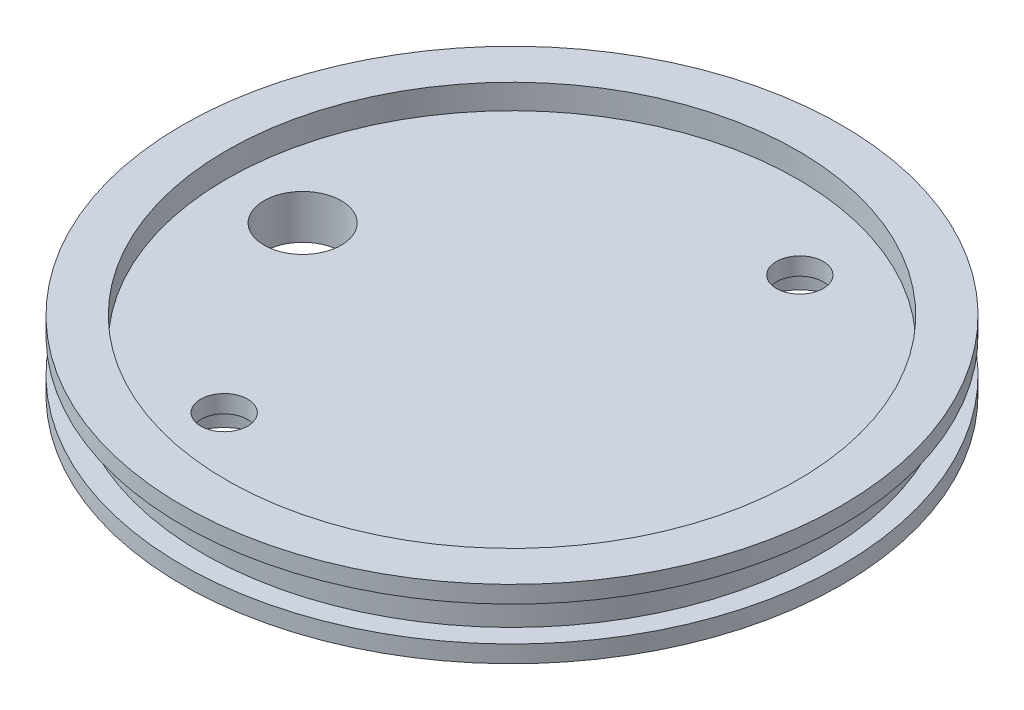
SolidWorks part; units mm, degrees
material "6061-T6 (SS)"
ref_plane "Front Plane" through (0, 0, 0) normal (0, 0, 1) x (1, 0, 0)
ref_plane "Top Plane" through (0, 0, 0) normal (0, 1, 0) x (1, 0, 0)
ref_plane "Right Plane" through (0, 0, 0) normal (1, 0, 0) x (0, 0, -1)
sketch "Sketch1" plane through (0, 0, 0) normal (0, 0, 1) x (1, 0, 0)
  line L0 (0, 48.1922) -> (0, -25.6743) construction
  line L1 (0, 0) -> (47.498, 0)
  line L2 (47.498, 0) -> (47.498, 2.4638)
  line L3 (47.498, 2.4638) -> (44.577, 2.4638)
  line L4 (44.577, 2.4638) -> (44.577, 7.4422)
  line L5 (44.577, 7.4422) -> (47.498, 7.4422)
  line L6 (47.498, 7.4422) -> (47.498, 9.906)
  line L7 (47.498, 9.906) -> (41.148, 9.906)
  line L8 (41.148, 9.906) -> (41.148, 6.35)
  line L9 (41.148, 6.35) -> (0, 6.35)
  line L10 (0, 6.35) -> (0, 0)
  dimension "D1" = 94.996
  dimension "D2" = 4.9784
  dimension "D3" = 2.921
  dimension "D4" = 9.906
  dimension "D5" = 6.35
  dimension "D6" = 6.35
revolve "Revolve1" add sketch "Sketch1" angle 360 about L0
hole_wizard "Tap Drill for 1/4 Tap - 1/4-18 NPT" positions "Sketch2" profile "Sketch3" hole size "1/4" standard "ANSI Inch" end condition through all
sketch "Sketch2" plane through (0, 6.35, 0) normal (0, 1, 0) x (1, 0, 0)
  point P0 (0, 0)
  point P3 (-30.1752, 0)
  dimension "D1" = 30.1752
sketch "Sketch3" plane through (0, 6.35, 0) normal (1, 0, 0) x (0, 0, 1)
  line L0 (0, 0) -> (0, 6.35)
  line L1 (0, 6.35) -> (5.5626, 6.35)
  line L2 (5.5626, 6.35) -> (5.5626, 0)
  line L5 (5.5626, 0) -> (0, 0)
  line L11 (0, -6.35) -> (0, 107.95) construction
  dimension "Thru Hole Dia." = 11.1252
  dimension "Thru Hole Depth" = 6.35
hole_wizard "CBORE for 1/4 Binding Head Machine Screw1" positions "Sketch4" profile "Sketch5" counterbore size "1/4" standard "ANSI Inch" end condition through all
sketch "Sketch4" plane through (0, 0, 0) normal (0, 1, 0) x (1, 0, 0)
  line L0 (0, 0) -> (-30.1752, 0)
  line L2 (0, 0) -> (12.1502, 29.3332)
  line L4 (0, 0) -> (-12.1502, -29.3332)
  point P0 (12.1502, 29.3332)
  point P2 (-12.1502, -29.3332)
  dimension "D1" = 31.75
  dimension "D2" = 112.5
sketch "Sketch5" plane through (12.1502, 0, -29.3332) normal (1, 0, 0) x (0, 0, -1)
  line L0 (0, 0) -> (0, 9.906)
  line L1 (0, 9.906) -> (3.3782, 9.906)
  line L3 (3.3782, 9.906) -> (3.3782, 3.81)
  line L4 (3.3782, 3.81) -> (6.35, 3.81)
  line L5 (6.35, 3.81) -> (6.35, 0)
  line L7 (6.35, 0) -> (0, 0)
  line L11 (0, -6.35) -> (0, 107.95) construction
  dimension "Thru Hole Dia." = 6.7564
  dimension "Thru Hole Depth" = 9.906
  dimension "C'Bore Dia." = 12.7
  dimension "C'Bore Depth" = 3.81
sketch "Sketch7" plane through (0, 6.35, 0) normal (0, 1, 0) x (1, 0, 0)
  circle A0 centre (0, 0) radius 11.1125
  dimension "D1" = 22.225
extrude "Boss-Extrude1" add sketch "Sketch7" against normal blind 6.35 contours A0
